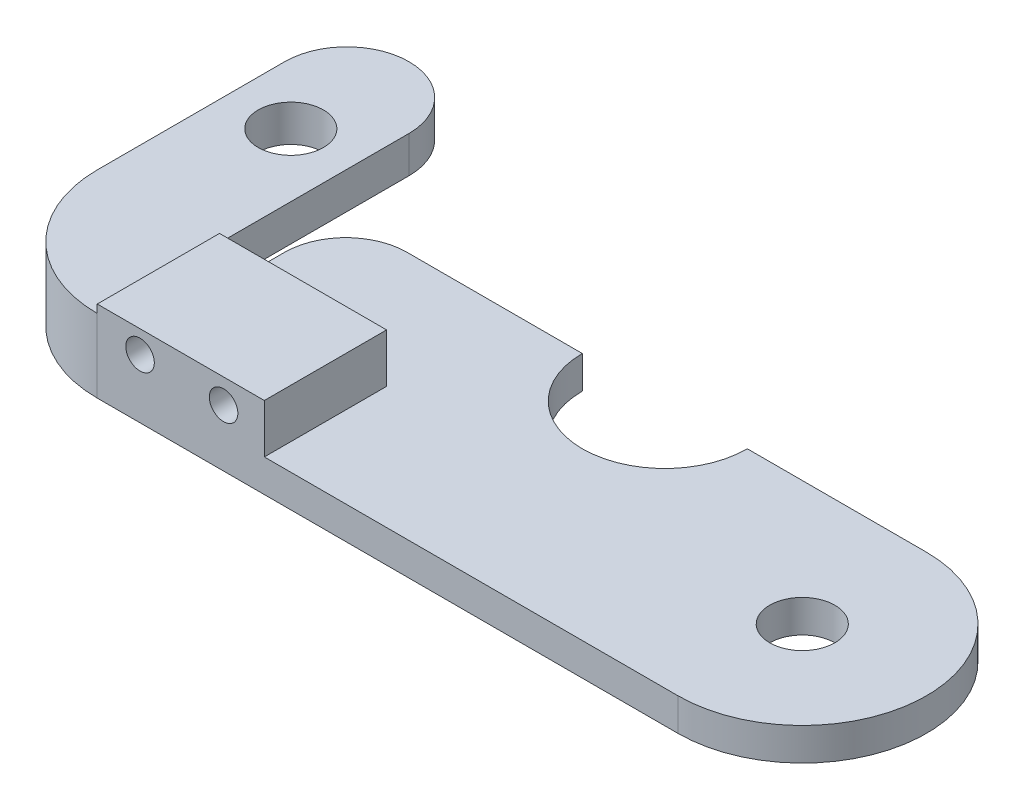
SolidWorks part; units mm, degrees
ref_plane "Front Plane" through (0, 0, 0) normal (0, 0, 1) x (1, 0, 0)
ref_plane "Top Plane" through (0, 0, 0) normal (0, 1, 0) x (1, 0, 0)
ref_plane "Right Plane" through (0, 0, 0) normal (1, 0, 0) x (0, 0, -1)
sketch "Sketch1" plane through (0, 0, 0) normal (0, 1, 0) x (1, 0, 0)
  line L0 (-13.6869, -1.9274) -> (14.8131, -1.9274)
  line L1 (14.8131, -1.9274) -> (14.8131, 4.1726) construction
  line L2 (14.8131, 10.2726) -> (6.0201, 10.2726)
  line L3 (-13.6869, 7.2726) -> (-13.6869, 4.1726)
  line L4 (-2.0799, 10.2726) -> (-10.6869, 10.2726)
  line L5 (-13.6869, 4.1726) -> (-19.7869, 4.1726) construction
  line L6 (-13.6869, 4.1726) -> (-13.6869, -1.9274)
  arc A0 (14.8131, -1.9274) -> (14.8131, 10.2726) centre (14.8131, 4.1726) ccw
  circle A1 centre (14.8131, 4.1726) radius 1.6
  arc A2 (-10.6869, 10.2726) -> (-13.6869, 7.2726) centre (-10.6869, 7.2726) ccw
  arc A3 (-2.0799, 10.2726) -> (6.0201, 10.2726) centre (1.9701, 10.2726) ccw
  arc A4 (-19.7869, 4.1726) -> (-13.6869, -1.9274) centre (-13.6869, 4.1726) ccw construction
  dimension "D3" = 3.2
  dimension "D4" = 6
  dimension "D5" = 8.1
  dimension "D1" = 28.5
  dimension "D2" = 6.1
  dimension "D6" = 6.1
  dimension "D7" = 11.607
extrude "Boss-Extrude1" add sketch "Sketch1" along normal blind 1.6
sketch "Sketch2" plane through (0, 1.6, 0) normal (0, 1, 0) x (1, 0, 0)
  line L1 (-13.6869, -1.9274) -> (-5.4869, -1.9274)
  line L2 (-13.6869, -1.9274) -> (-13.6869, 4.0726)
  line L3 (-13.6869, 4.0726) -> (-5.4869, 4.0726)
  line L4 (-5.4869, -1.9274) -> (-5.4869, 4.0726)
  dimension "D1" = 8.2
  dimension "D2" = 6
extrude "Boss-Extrude2" add sketch "Sketch2" along normal blind 2.4
sketch "Sketch3" plane through (0, 0, 1.9274) normal (0, 0, 1) x (1, 0, 0)
  line L0 (-5.4869, 4) -> (-5.4869, 1.6) construction
  line L1 (-13.6869, 4) -> (-5.4869, 4) construction
  circle A0 centre (-11.5857, 2.9) radius 0.7
  circle A1 centre (-7.4869, 2.8) radius 0.7
  dimension "D1" = 1.4
  dimension "D2" = 1.4
  dimension "D3" = 2
  dimension "D4" = 4.1
  dimension "D5" = 1.2
extrude "Cut-Extrude1" cut sketch "Sketch3" against normal up to surface (6 mm away) up to face at (-9.5869, 2.8, -4.0726)
ref_plane "Plane1" through (0, 1.8, 0) normal (0, 1, 0) x (1, 0, 0)
sketch "Sketch4" plane through (0, 0, 0) normal (0, -1, 0) x (1, 0, 0)
  line L0 (-13.6869, 1.9274) -> (-13.6869, -4.1726)
  line L2 (-13.6869, -4.1726) -> (-19.7869, -4.1726)
  arc A0 (-13.6869, 1.9274) -> (-19.7869, -4.1726) centre (-13.6869, -4.1726) ccw
  dimension "D1" = 6.1
extrude "Boss-Extrude3" add sketch "Sketch4" against normal blind 3.6 separate body
sketch "Sketch5" plane through (0, 0, -4.1726) normal (0, 0, -1) x (-1, 0, 0)
  line L0 (19.7869, 3.6) -> (19.7869, 0) construction
  line L1 (13.6869, 3.6) -> (19.7869, 3.6)
  line L2 (13.6869, 3.6) -> (13.6869, 1.8)
  line L3 (13.6869, 1.8) -> (19.7869, 1.8)
  line L4 (19.7869, 3.6) -> (19.7869, 1.8)
  line L5 (2.0799, 1.6) -> (10.6869, 1.6) construction
  dimension "D1" = 0.2
extrude "Boss-Extrude4" add sketch "Sketch5" along normal blind 9.2
sketch "Sketch6" plane through (0, 3.6, 0) normal (0, 1, 0) x (1, 0, 0)
  line L0 (-19.7869, 13.3726) -> (-13.6869, 13.3726) construction
  line L1 (-19.7869, 13.3726) -> (-13.6869, 13.3726)
  arc A0 (-13.6869, 13.3726) -> (-19.7869, 13.3726) centre (-16.7369, 13.3726) ccw
extrude "Boss-Extrude5" add sketch "Sketch6" against normal up to surface (1.8 mm away) up to face at (-16.7369, 1.8, -8.7726)
sketch "Sketch7" plane through (0, 3.6, 0) normal (0, 1, 0) x (1, 0, 0)
  line L0 (-19.7869, 13.3726) -> (-19.7869, 4.1726) construction
  circle A0 centre (-16.7869, 10.6726) radius 1.6
  arc A2 (-13.6869, 13.3726) -> (-19.7869, 13.3726) centre (-16.7369, 13.3726) ccw construction
  dimension "D2" = 3.2
  dimension "D1" = 3
  dimension "D3" = 2.7
extrude "Cut-Extrude2" cut sketch "Sketch7" against normal up to surface (1.8 mm away) up to face at (-16.7369, 1.8, -9.5351)
